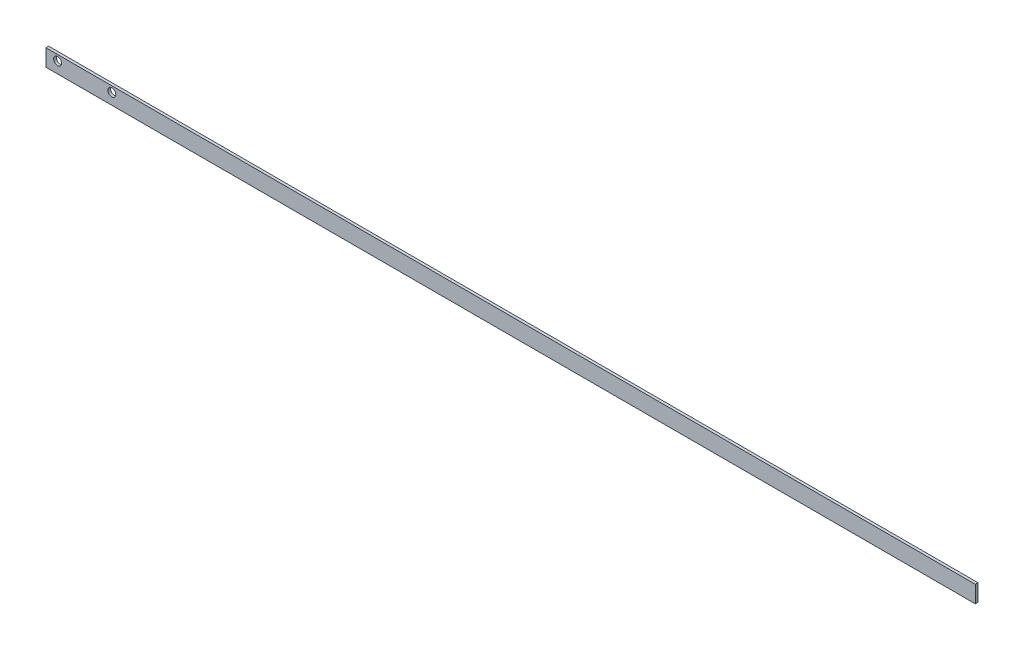
SolidWorks part; units mm, degrees
ref_plane "Front Plane" through (0, 0, 0) normal (0, 0, 1) x (1, 0, 0)
ref_plane "Top Plane" through (0, 0, 0) normal (0, 1, 0) x (1, 0, 0)
ref_plane "Right Plane" through (0, 0, 0) normal (1, 0, 0) x (0, 0, -1)
sketch "Sketch1" plane through (0, 0, 0) normal (0, 0, 1) x (1, 0, 0)
  line L1 (-304.8, -5.5499) -> (304.8, -5.5499)
  line L2 (-304.8, -5.5499) -> (-304.8, 5.5499)
  line L3 (-304.8, 5.5499) -> (304.8, 5.5499)
  line L4 (304.8, -5.5499) -> (304.8, 5.5499)
  line L5 (-304.8, -5.5499) -> (304.8, 5.5499) construction
  line L6 (-304.8, 5.5499) -> (304.8, -5.5499) construction
  point P0 (0, 0)
  dimension "D1" = 609.6
  dimension "D2" = 11.0998
extrude "Boss-Extrude1" add sketch "Sketch1" along normal mid plane 1.778
sketch "Sketch2" plane through (0, 0, 0.889) normal (0, 0, 1) x (1, 0, 0)
  line L0 (304.8, 5.5499) -> (-304.8, 5.5499) construction
  line L1 (-304.8, 5.5499) -> (-304.8, -5.5499) construction
  circle A0 centre (-297.18, 1.7399) radius 1.651
  circle A1 centre (-261.62, 1.7399) radius 1.651
  point P8 (0, 0)
  dimension "D2" = 3.302
  dimension "D1" = 3.81
  dimension "D3" = 7.62
  dimension "D4" = 35.56
hole_wizard "#6 (0.204) Diameter Hole1" positions "Sketch3" profile "Sketch4" hole size "#6" standard "ANSI Inch" end condition through all
sketch "Sketch3" plane through (0, 0, 0.889) normal (0, 0, 1) x (1, 0, 0)
  point P0 (-297.18, 1.7399)
  point P3 (-261.62, 1.7399)
sketch "Sketch4" plane through (-297.18, 1.7399, 0.889) normal (1, 0, 0) x (0, -1, 0)
  line L0 (0, 0) -> (0, 1.778)
  line L1 (0, 1.778) -> (2.5908, 1.778)
  line L2 (2.5908, 1.778) -> (2.5908, 0)
  line L5 (2.5908, 0) -> (0, 0)
  line L11 (0, -6.35) -> (0, 107.95) construction
  dimension "Thru Hole Dia." = 5.1816
  dimension "Thru Hole Depth" = 1.778
